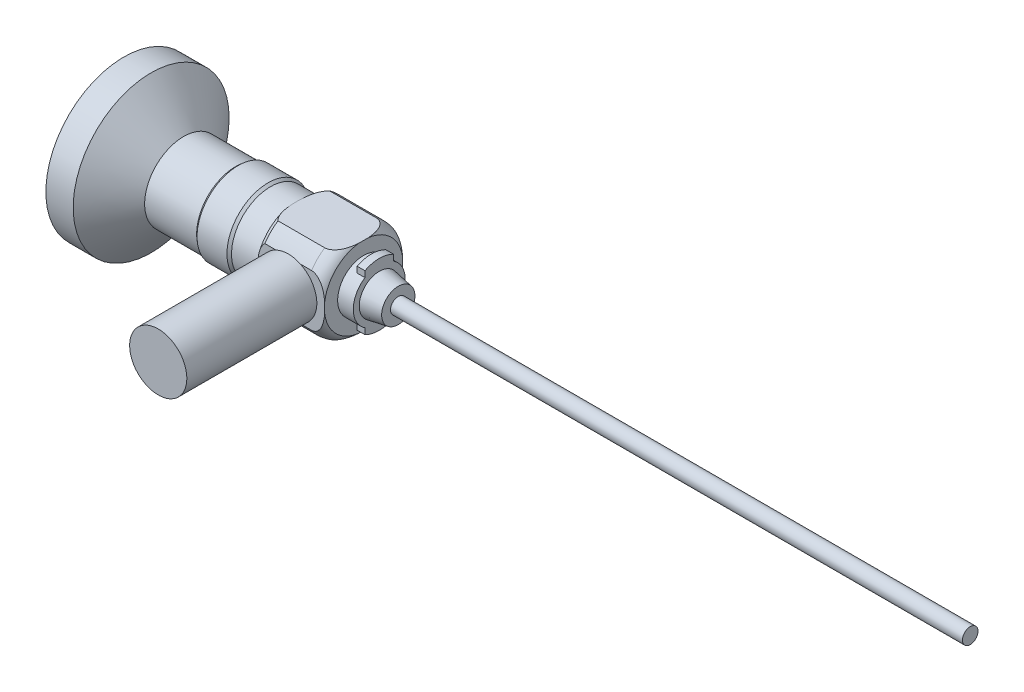
SolidWorks part; units mm, degrees
ref_plane "Front Plane" through (0, 0, 0) normal (0, 0, 1) x (1, 0, 0)
ref_plane "Top Plane" through (0, 0, 0) normal (0, 1, 0) x (1, 0, 0)
ref_plane "Right Plane" through (0, 0, 0) normal (1, 0, 0) x (0, 0, -1)
ref_axis "Axis1" through (88.99, 0, 0) along (-1, 0, 0)
sketch "Sketch1" plane through (0, 0, 0) normal (0, 0, 1) x (1, 0, 0)
  line L0 (-74.5697, 0) -> (-77.8697, -15) construction
  line L1 (-77.8697, -15) -> (-72.6197, -15)
  line L2 (-72.6197, -15) -> (-66.3697, -7.5)
  line L3 (-66.3697, -7.5) -> (-56.3697, -7.5)
  line L4 (-56.3697, -7.5) -> (-55.8897, -7.9)
  line L5 (-55.8897, -7.9) -> (-50.1397, -7.9)
  line L6 (-50.1397, -7.9) -> (-49.6597, -7.5)
  line L7 (-49.6597, -7.5) -> (-44.6597, -7.5)
  line L8 (88.99, 0) -> (-88.99, 0) construction
  line L9 (-74.5697, 0) -> (-25.0835, 0)
  line L10 (-43.2452, -9) -> (-34.2597, -9)
  line L11 (-31.7461, -7.5592) -> (-31.7461, -5)
  line L12 (-31.7461, -5) -> (-30.2461, -5)
  line L13 (-30.2461, -5) -> (-30.2461, -6)
  line L14 (-30.2461, -6) -> (-28.7461, -6)
  line L15 (-28.7461, -6) -> (-28.7461, -3.85)
  line L16 (-28.7461, -3.85) -> (-25.0835, -3.2)
  line L17 (-25.0835, -3.2) -> (-25.0835, 0)
  arc A0 (-74.5697, 0) -> (-77.8697, -15) centre (-129.3209, 4.1823) cw
  arc A1 (-44.6597, -7.5) -> (-40.5597, -9) centre (-41.9025, -6.3168) ccw
  arc A2 (-34.2597, -9) -> (-31.7461, -7.5592) centre (-34.3096, -6) ccw
  point P12 (-40.5597, -9)
  point P16 (-34.2597, -9)
  point P17 (-44.6597, -9)
  point P18 (-37.4097, -9)
  point P20 (-30.1597, -9)
  dimension "D4" = 11.5
  dimension "D12" = 9
  dimension "D13" = 3.15
  dimension "D15" = 5
  dimension "D1" = 5.25
  dimension "D2" = 15
  dimension "D3" = 3.3
  dimension "D5" = 7.5
  dimension "D6" = 5.75
  dimension "D7" = 7.9
  dimension "D8" = 7.5
  dimension "D9" = 10
  dimension "D10" = 5
  dimension "D11" = 14.5
  dimension "D14" = 3.15
  dimension "D16" = 6
  dimension "D17" = 1.5
  dimension "D18" = 1.5
  dimension "D19" = 3.85
  dimension "D20" = 3.2
revolve "Revolve1" add sketch "Sketch1" angle 360 about axis through (88.99, 0, 0) along (-1, 0, 0) region at (-53.5304, -4.7691, 0)
sketch "Sketch2" plane through (-31.7461, 0, 0) normal (1, 0, 0) x (0, 0, -1)
  line L0 (0, 9) -> (0, -9)
  line L1 (12.4327, -7.5) -> (-12.4327, -7.5)
  line L2 (12.4327, -7.5) -> (12.4327, 7.5) construction
  line L3 (12.4327, 7.5) -> (-12.4327, 7.5)
  line L4 (-12.4327, -7.5) -> (-12.4327, 7.5) construction
  line L5 (12.4327, 7.5) -> (-12.4327, -7.5) construction
  line L6 (12.4327, 7.5) -> (12.4327, 11.5013)
  line L7 (12.4327, 11.5013) -> (-12.4327, 11.5013)
  line L8 (-12.4327, 11.5013) -> (-12.4327, 7.5)
  line L9 (-12.4327, -7.5) -> (-12.4327, -12.9232)
  line L10 (-12.4327, -12.9232) -> (12.4327, -12.9232)
  line L11 (12.4327, -12.9232) -> (12.4327, -7.5)
  circle A0 centre (0, 0) radius 9 construction
  circle A1 centre (0, 0) radius 9
  dimension "D1" = 15
extrude "Cut-Extrude1" cut sketch "Sketch2" against normal blind 15 contours L9 L10 L11 L1 | L8 L3 L6 L7
pattern_circular "CirPattern1" count 2 every 90 about axis through (88.99, 0, 0) along (-1, 0, 0) of "Cut-Extrude1"
sketch "Sketch3" plane through (-28.7461, 0, 0) normal (1, 0, 0) x (0, 0, -1)
  line L0 (2.75, 6.4372) -> (2.75, -6.4372) construction
  line L1 (-2.75, -6.4372) -> (-2.75, 6.4372) construction
  line L2 (2.75, -6.4372) -> (-2.75, 6.4372) construction
  line L3 (2.75, -4.1758) -> (2.75, -6.4372)
  line L4 (2.75, -6.4372) -> (-2.75, -6.4372) construction
  line L5 (-2.75, -6.4372) -> (-2.75, -4.1758)
  line L6 (2.75, 4.1758) -> (2.75, 6.4372)
  line L7 (2.75, 6.4372) -> (-2.75, 6.4372) construction
  line L8 (-2.75, 6.4372) -> (-2.75, 4.1758)
  line L9 (2.75, 6.4372) -> (6.4302, 6.4372)
  line L10 (6.4302, 6.4372) -> (5.9638, -6.4372)
  line L11 (5.9638, -6.4372) -> (2.75, -6.4372)
  line L12 (-2.75, -6.4372) -> (-6.2806, -6.4372)
  line L13 (-6.2806, -6.4372) -> (-6.2806, 6.4372)
  line L14 (-6.2806, 6.4372) -> (-2.75, 6.4372)
  circle A0 centre (0, 0) radius 6 construction
  circle A1 centre (0, 0) radius 6 construction
  arc A2 (2.75, -4.1758) -> (2.75, 4.1758) centre (0, 0) ccw
  arc A3 (-2.75, 4.1758) -> (-2.75, -4.1758) centre (0, 0) ccw
  point P3 (7, 0)
  point P4 (0, 0)
  dimension "D1" = 10
  dimension "D3" = 5.5
extrude "Cut-Extrude2" cut sketch "Sketch3" against normal up to surface (1.5 mm away) up to face at (-30.2461, 0, -6)
sketch "Sketch4" plane through (0, 0, 7.5) normal (0, 0, 1) x (1, 0, 0)
  line L0 (-34.2597, 4.9749) -> (-43.2452, -4.9749) construction
  circle A0 centre (-38.7525, 0) radius 5.5
  dimension "D1" = 11
extrude "Boss-Extrude1" add sketch "Sketch4" along normal blind 25
sketch "Sketch5" plane through (-25.0835, 0, 0) normal (1, 0, 0) x (0, 0, -1)
  circle A0 centre (0, 0) radius 1.5
  dimension "D1" = 3
extrude "Boss-Extrude2" add sketch "Sketch5" along normal blind 110
